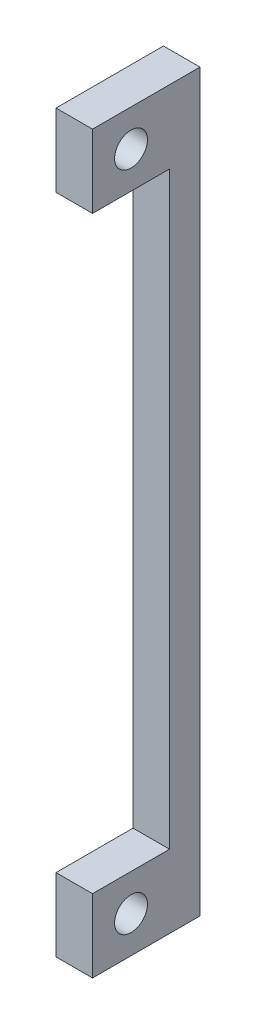
SolidWorks part; units mm, degrees
ref_plane "Přední rovina" through (0, 0, 0) normal (0, 0, 1) x (1, 0, 0)
ref_plane "Horní rovina" through (0, 0, 0) normal (0, 1, 0) x (1, 0, 0)
ref_plane "Pravá rovina" through (0, 0, 0) normal (1, 0, 0) x (0, 0, -1)
sketch "Skica2" plane through (0, 0, 0) normal (0, 0, 1) x (1, 0, 0)
  line L0 (-3, -6) -> (0, -6)
  line L1 (0, 0) -> (-3, 0)
  line L2 (0, 0) -> (0, -60.4)
  line L3 (0, -60.4) -> (-3, -60.4)
  line L4 (-3, 0) -> (-3, -60.4)
  line L5 (-3, -54.4) -> (0, -54.4)
  point P7 (-1.5, 0)
  dimension "D1" = 60.4
  dimension "D2" = 3
  dimension "D3" = 6
  dimension "D4" = 6
extrude "Přidat vysunutím1" add sketch "Skica2" along normal blind 2.5 contours L4 L5 L2 L0 | L1 L4 L0 L2 | L5 L4 L3 L2 region at (-1.5, -3, 0) region at (-1.5, -30.2, 0) region at (-1.5, -57.4, 0)
extrude "Přidat vysunutím2" add sketch "Skica2<3>" along normal blind 8.8275 contours L1 L4 L0 L2 | L5 L4 L3 L2 region at (-1.5, -3, 0) region at (-1.5, -57.4, 0)
sketch "Skica2<3>" plane through (0, 0, 0) normal (0, 0, 1) x (1, 0, 0) same geometry as "Skica2"
sketch "Skica3" plane through (-3, 0, 0) normal (-1, 0, 0) x (0, 0, 1)
  line L0 (8.8275, 0) -> (0, 0) construction
  line L1 (8.8275, 0) -> (8.8275, -6) construction
  line L2 (8.8275, -54.4) -> (2.5, -54.4) construction
  circle A0 centre (5.6638, -3) radius 1.35
  circle A1 centre (5.6638, -57.4) radius 1.35
  dimension "D3" = 2.7
  dimension "D5" = 2.7
  dimension "D1" = 3
  dimension "D2" = 3.1637
  dimension "D4" = 3
extrude "Odebrat vysunutím1" cut sketch "Skica3" against normal blind 8.8275
